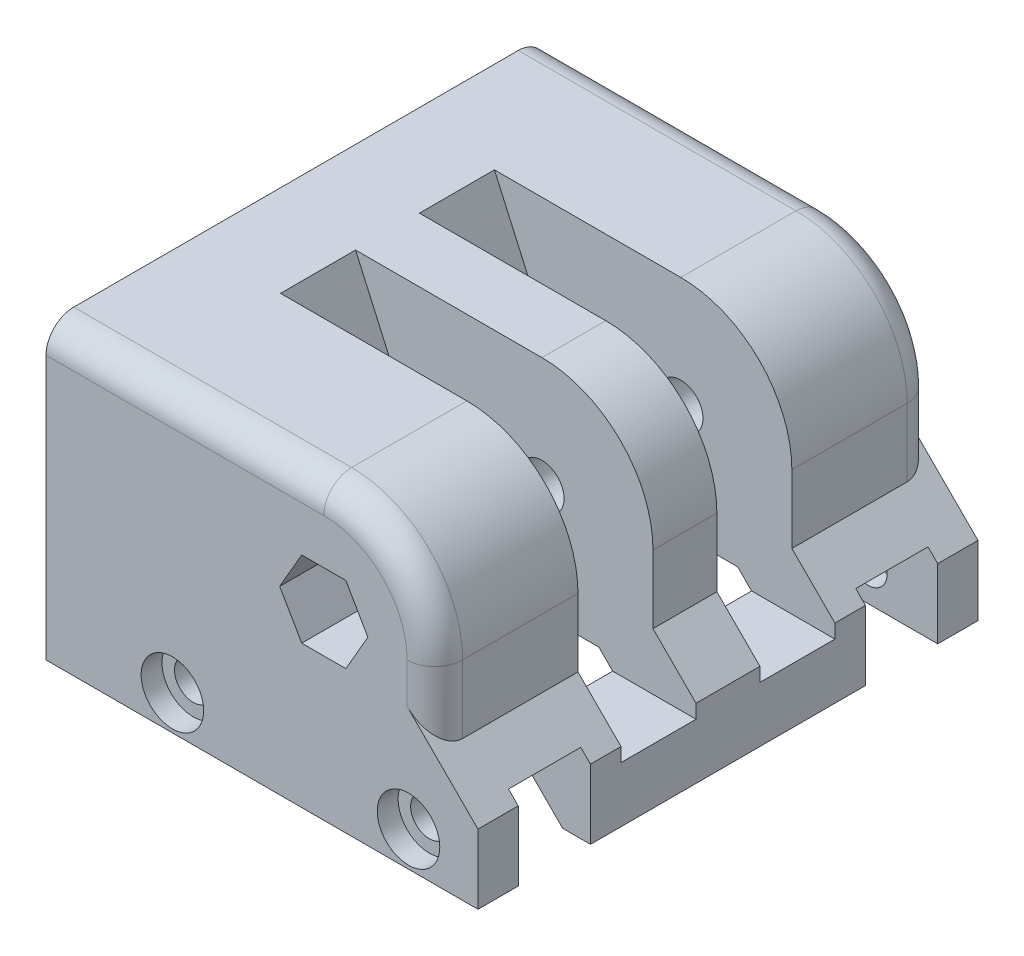
SolidWorks part; units mm, degrees
ref_plane "Front Plane" through (0, 0, 0) normal (0, 0, 1) x (1, 0, 0)
ref_plane "Top Plane" through (0, 0, 0) normal (0, 1, 0) x (1, 0, 0)
ref_plane "Right Plane" through (0, 0, 0) normal (1, 0, 0) x (0, 0, -1)
sketch "Sketch1" plane through (0, 0, 0) normal (0, 0, 1) x (1, 0, 0)
  line L7 (-20, 5.5538) -> (-20, -8)
  line L8 (-20, -8) -> (11.1, -8) construction
  line L11 (-20, 5.5538) -> (-20, 8)
  line L14 (0, 8) -> (-20, 8)
  line L15 (-20, -8) -> (-20, -13)
  line L16 (-20, -13) -> (11.1, -13)
  line L21 (11.1, -8) -> (11.1, -13)
  line L26 (11.1, -15.5145) -> (11.1, -35.4581) construction
  line L27 (-17, -50.9163) -> (-17, 49949.0837) construction
  line L28 (8, 0) -> (8, -4.9)
  line L29 (8, -4.9) -> (11.1, -8)
  line L30 (-10.9, -10.5) -> (6.1, -10.5) construction
  circle A5 centre (0, 0) radius 1.55 construction
  circle A10 centre (-10.9, -10.5) radius 1.35 construction
  circle A11 centre (6.1, -10.5) radius 1.35 construction
  circle A12 centre (0, 0) radius 8 construction
  arc A13 (0, 8) -> (8, 0) centre (0, 0) cw
  dimension "D1" = 8
  dimension "D2" = 9.1
  dimension "D3" = 8
  dimension "D4" = 20
  dimension "D6" = 3.1
  dimension "D7" = 17
  dimension "D8" = 5
  dimension "D9" = 45
  dimension "D12" = 2.7
  dimension "D16" = 8
  dimension "D13" = 2.5
  dimension "D5" = 5
extrude "Boss-Extrude1" add sketch "Sketch1" along normal blind 18
sketch "Croquis2" plane through (0, 0, 18) normal (0, 0, 1) x (1, 0, 0)
  circle A0 centre (-10.9, -10.5) radius 1.35
  circle A1 centre (6.1, -10.5) radius 1.35
extrude "Cortar-Extruir2" cut sketch "Croquis2" against normal blind 5
sketch "Sketch3" plane through (0, 0, 18) normal (0, 0, 1) x (1, 0, 0)
  circle A5 centre (-10.9, -10.5) radius 2.25
  circle A6 centre (6.1, -10.5) radius 2.25
extrude "Cut-Extrude1" cut sketch "Sketch3" against normal blind 1.5
sketch "Sketch5" plane through (11.1, 0, 0) normal (1, 0, 0) x (0, 0, -1)
  line L0 (-18, -13) -> (0, -13) construction
  line L1 (-15.1, -13) -> (-9.9, -13)
  line L2 (-15.1, -13) -> (-15.1, -7.3)
  line L3 (-15.1, -7.3) -> (-9.9, -7.3)
  line L4 (-9.9, -13) -> (-9.9, -7.3)
  line L5 (-18, -13) -> (-18, -8) construction
  dimension "D1" = 2.9
  dimension "D2" = 5.2
  dimension "D3" = 5.7
extrude "Cut-Extrude2" cut sketch "Sketch5" against normal through all
sketch "Sketch6" plane through (0, 0, 18) normal (0, 0, 1) x (1, 0, 0)
  line L0 (-13.4136, 8) -> (-8.2219, -3.6606)
  line L2 (0, -9) -> (14.4338, -9)
  line L5 (-13.4136, 8) -> (0, 8)
  line L6 (6.9282, 4) -> (14.4338, -9)
  arc A0 (-8.2219, -3.6606) -> (0, -9) centre (0, 0) ccw
  arc A1 (0, 8) -> (6.9282, 4) centre (0, 0) cw
  dimension "D1" = 9
  dimension "D2" = 66
extrude "Cut-Extrude3" cut sketch "Sketch6" against normal blind 5.4 from offset 10.3 offset against normal yes
sketch "Croquis1" plane through (0, 0, 0) normal (0, 0, -1) x (-1, 0, 0)
  circle A0 centre (0, 0) radius 1.6
  dimension "D1" = 3.2
extrude "Cortar-Extruir1" cut sketch "Croquis1" against normal through all
sketch "Sketch10" plane through (0, 0, 18) normal (0, 0, 1) x (1, 0, 0)
  line L1 (3.1754, 0) -> (1.5877, 2.75)
  line L2 (1.5877, 2.75) -> (-1.5877, 2.75)
  line L3 (-1.5877, 2.75) -> (-3.1754, 0)
  line L4 (-3.1754, 0) -> (-1.5877, -2.75)
  line L5 (-1.5877, -2.75) -> (1.5877, -2.75)
  line L6 (1.5877, -2.75) -> (3.1754, 0)
  circle A0 centre (0, 0) radius 2.75 construction
  dimension "D1" = 5.5
extrude "Cut-Extrude7" cut sketch "Sketch10" against normal blind 5
mirror "Mirror1" about plane through (0, 0, 0) normal (0, 0, -1) of "Cut-Extrude7", "Cortar-Extruir1", "Cortar-Extruir2", "Cut-Extrude1", "Boss-Extrude1", "Cut-Extrude2", "Cut-Extrude3"
sketch "Sketch7" plane through (0, -13, 0) normal (0, -1, 0) x (1, 0, 0)
  line L0 (-20, 9.9) -> (11.1, 9.9) construction
  line L1 (-20, 9.9) -> (4.1, 9.9)
  line L2 (-20, 9.9) -> (-20, -9.9)
  line L3 (-20, -9.9) -> (4.1, -9.9)
  line L4 (4.1, 9.9) -> (4.1, -9.9)
  line L5 (-20, -9.9) -> (11.1, -9.9) construction
  line L6 (11.1, 9.9) -> (11.1, -9.9) construction
  line L7 (-20, 9.9) -> (-20, -9.9) construction
  dimension "D2" = 7
extrude "Cut-Extrude4" cut sketch "Sketch7" against normal blind 5
fillet "Fillet5" radius 2 4 edges at (5.6569, 5.6569, 18) (-10, 8, -18) (-10, 8, 18) (8, -2.45, 18)
chamfer "Chaflán1" distance 5 angle 45 1 edges at (4.1, -13, 0)
